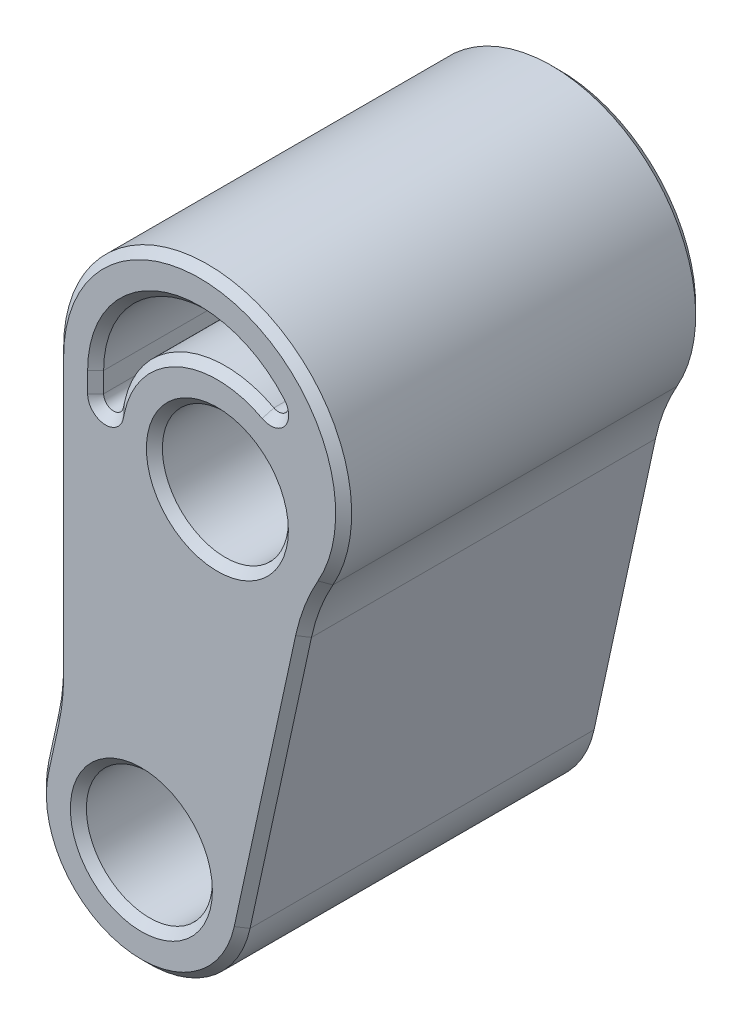
SolidWorks part; units mm, degrees
ref_plane "Front" through (0, 0, 0) normal (0, 0, 1) x (1, 0, 0)
ref_plane "Top" through (0, 0, 0) normal (0, 1, 0) x (1, 0, 0)
ref_plane "Right" through (0, 0, 0) normal (1, 0, 0) x (0, 0, -1)
sketch "Sketch1" plane through (0, 0, 0) normal (0, 0, 1) x (1, 0, 0)
  line L3 (-2.575, 0) -> (-1.575, 0) construction
  line L23 (-0.325, -8.75) -> (0.675, -8.75) construction
  line L33 (-2.5164, 0.5464) -> (-4.4164, -8.2036)
  line L34 (0.6164, -9.2964) -> (2.5164, -0.5464)
  circle A0 centre (0, 0) radius 2.575 construction
  circle A3 centre (0, 0) radius 1.575
  circle A12 centre (-1.9, -8.75) radius 1.575
  circle A13 centre (-1.9, -8.75) radius 4 construction
  arc A22 (-2.5164, 0.5464) -> (2.5164, -0.5464) centre (0, 0) cw
  arc A28 (-4.4164, -8.2036) -> (0.6164, -9.2964) centre (-1.9, -8.75) ccw
  dimension "D1" = 3.15
  dimension "D3" = 8
  dimension "D2" = 1
  dimension "D6" = 8.75
  dimension "D4" = 1.9
extrude "Boss-Extrude1" add sketch "Sketch1" along normal mid plane 9 contours A3 region at (-0.95, -4.375, 0)
sketch "Sketch2" plane through (0, 0, 0) normal (0, 0, 1) x (1, 0, 0)
  line L0 (-4.0437, -6.4876) -> (-4.0437, 0.9516)
  line L1 (0, 0) -> (0, 8.0844) construction
  line L2 (0, 0) -> (-0.4437, 0.9516) construction
  line L3 (-0.4437, 0.9516) -> (-1.7961, 3.8518) construction
  line L4 (-1.7961, 3.8518) -> (-1.9652, 4.2143) construction
  line L5 (-2.5164, 0.5464) -> (-4.4164, -8.2036) construction
  line L6 (-2.5164, 0.5464) -> (-4.4164, -8.2036) construction
  arc A0 (-4.0437, 0.9516) -> (1.65, -1.9769) centre (-0.4437, 0.9516) cw
  circle A1 centre (0, 0) radius 4.25 construction
  arc A4 (2.5164, -0.5464) -> (-2.5164, 0.5464) centre (0, 0) ccw construction
  point P5 (-4.2791, -5.2153)
  point P18 (1.5664, -2.0593)
  point P19 (-4.0088, 1.0052)
  point P20 (1.5809, -2.0326)
  point P21 (1.1436, -2.3071)
  point P22 (1.2837, -2.2322)
  point P23 (-4.0284, -0.5054)
  point P24 (-4.1114, -6.7993)
  point P25 (-2.0188, 4.1889)
  point P26 (1.2034, -2.2765)
  point P27 (0, 0)
  point P28 (-4.1446, 0.9407)
  point P29 (1.575, -2.0341)
  dimension "D2" = 8.5
  dimension "D4" = 3.6
  dimension "D1" = 0.4
  dimension "D3" = 25
extrude "Spring" add sketch "Sketch2" along normal through all and the other way through all thin thin type one direction wall 1
fillet "Spring Inside Fillets" radius 0.25 2 edges at (-3.0437, -1.8824, 0) (2.0998, 1.4905, 0)
fillet "Spring Outside Fillets" radius 5 2 edges at (-4.0437, -6.4876, 0) (2.3481, -1.3211, 0)
chamfer "Deburs" distance 0.2 angle 45 30 edges at (1.575, 0, -4.5) (-0.325, -8.75, -4.5) (-1.3531, 3.3874, -4.5) (1.5267, 2.3357, -4.5) (-2.8204, 0.1985, -4.5) (-3.0437, 0.6994, -4.5) (-2.4464, -11.2664, -4.5) (1.3836, -5.7632, -4.5) (-1.0807, 2.3372, -4.5) (0.4746, 4.4325, -4.5) (-4.0437, -2.4997, -4.5) (-4.0723, -6.4846, -4.5) (-4.287, -7.6078, -4.5) (-0.325, -8.75, 4.5) (1.575, 0, 4.5) (1.5267, 2.3357, 4.5) (-1.3531, 3.3874, 4.5) (-3.0437, 0.6994, 4.5) (-2.8204, 0.1985, 4.5) (0.4746, 4.4325, 4.5) (-1.0807, 2.3372, 4.5) (1.3836, -5.7632, 4.5) (-2.4464, -11.2664, 4.5) (-4.287, -7.6078, 4.5) (-4.0723, -6.4846, 4.5) (-4.0437, -2.4997, 4.5) (-2.5329, 0.4702, -4.5) (-2.5329, 0.4702, 4.5) (2.3661, -1.5069, -4.5) (2.3661, -1.5069, 4.5)
equation "\"D1@Sketch1\"=\"Hardware Clearance Hole Diameter@Box Assy.Assembly\""
